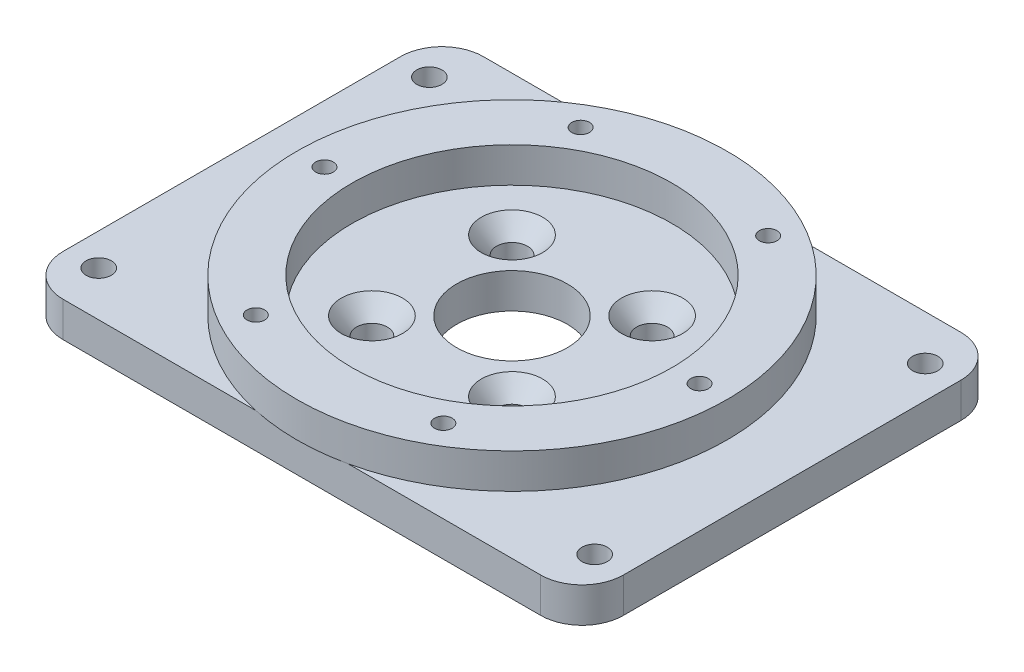
SolidWorks part; units mm, degrees
other "mainValvePlate"
other "motorRingMount"
ref_plane "Front Plane" through (0, 0, 0) normal (0, 0, 1) x (1, 0, 0)
ref_plane "Top Plane" through (0, 0, 0) normal (0, 1, 0) x (1, 0, 0)
ref_plane "Right Plane" through (0, 0, 0) normal (1, 0, 0) x (0, 0, -1)
sketch "Sketch1" plane through (0, 0, 0) normal (0, 1, 0) x (1, 0, 0)
  line L0 (0, 0) -> (0, -19.6757) construction
  line L6 (-50.8, -38.1) -> (50.8, -38.1)
  line L7 (0, 0) -> (-17, -29.4449) construction
  line L8 (0, 0) -> (-34, 0) construction
  line L9 (0, 0) -> (-17, 29.4449) construction
  line L10 (0, 0) -> (17, 29.4449) construction
  line L11 (0, 0) -> (34, 0) construction
  line L12 (0, 0) -> (17, -29.4449) construction
  line L13 (-50.8, -38.1) -> (-50.8, 38.1)
  line L14 (-50.8, 38.1) -> (50.8, 38.1)
  line L15 (50.8, -38.1) -> (50.8, 38.1)
  line L16 (-50.8, -38.1) -> (50.8, 38.1) construction
  line L17 (-50.8, 38.1) -> (50.8, -38.1) construction
  circle A0 centre (0, 0) radius 34 construction
  point P0 (0, 0)
  point P8 (0, -34)
  point P9 (44.958, -29.972)
  point P12 (-17, -29.4449)
  point P13 (-44.958, -29.972)
  point P20 (-44.958, 29.972)
  point P22 (44.958, 29.972)
  dimension "D1" = 68
  dimension "D2" = 76.2
  dimension "D3" = 101.6
  dimension "D4" = 30
  dimension "D5" = 6
  dimension "D6" = 44.958
  dimension "D7" = 29.972
extrude "Boss-Extrude1" add sketch "Sketch1" along normal blind 6.35
sketch "Sketch4" plane through (0, 0, 0) normal (0, -1, 0) x (1, 0, 0)
  circle A0 centre (-44.958, 29.972) radius 2.286
  circle A1 centre (-44.958, -29.972) radius 2.286
  circle A2 centre (44.958, -29.972) radius 2.286
  circle A3 centre (44.958, 29.972) radius 2.286
  circle A5 centre (0, 0) radius 10.033
  dimension "D1" = 4.572
  dimension "D2" = 20.066
extrude "Cut-Extrude1" cut sketch "Sketch4" against normal through all contours A0 | A1 | A2 | A3 | A5 region at (-44.958, 0, 29.972) region at (-44.958, 0, -29.972) region at (44.958, 0, -29.972) region at (44.958, 0, 29.972) region at (0, 0, 0)
sketch "Sketch6" plane through (0, 6.35, 0) normal (0, 1, 0) x (1, 0, 0)
  line L1 (-12.7, -12.7) -> (12.7, -12.7) construction
  line L2 (-12.7, -12.7) -> (-12.7, 12.7) construction
  line L3 (-12.7, 12.7) -> (12.7, 12.7) construction
  line L4 (12.7, -12.7) -> (12.7, 12.7) construction
  line L5 (-12.7, -12.7) -> (12.7, 12.7)
  line L6 (-12.7, 12.7) -> (12.7, -12.7)
  line L7 (0, 0) -> (0, 18.6441) construction
  line L8 (0, -41.91) -> (0, 41.91) construction
  point P0 (0, 0)
  point P1 (12.7, 12.7)
  point P2 (-12.7, -12.7)
  point P3 (-12.7, 12.7)
  point P4 (12.7, -12.7)
  dimension "D1" = 25.4
hole_wizard "CSK for #12 Flat Head Machine Screw3" positions "Sketch6" profile "Sketch10" countersink size "#12" standard "ANSI Inch" end condition up to next
sketch "Sketch10" plane through (12.7, 6.35, 12.7) normal (1, 0, 0) x (0, 0, 1)
  line L0 (0, 0) -> (0, 6.35)
  line L1 (0, 6.35) -> (2.8067, 6.35)
  line L2 (2.8067, 6.35) -> (2.8067, 3.1703)
  line L3 (2.8067, 3.1703) -> (5.5626, 0)
  line L5 (5.5626, 0) -> (0, 0)
  line L6 (-2.8067, 3.1703) -> (-5.5626, 0) construction
  line L11 (0, -6.35) -> (0, 107.95) construction
  dimension "Thru Hole Dia." = 5.6134
  dimension "Thru Hole Depth" = 6.35
  dimension "Near C'Sink Dia." = 11.1252
  dimension "Near C'Sink Angle" = 82
fillet "Fillet1" radius 7.5 4 edges at (50.8, 3.175, 38.1) (50.8, 3.175, -38.1) (-50.8, 3.175, -38.1) (-50.8, 3.175, 38.1)
sketch "Sketch12" plane through (0, 6.35, 0) normal (0, 1, 0) x (1, 0, 0)
  line L0 (34, 0) -> (39, 0) construction
  line L1 (34, 0) -> (29, 0) construction
  circle A0 centre (0, 0) radius 39
  circle A1 centre (0, 0) radius 29
  dimension "D1" = 5
extrude "Boss-Extrude3" add sketch "Sketch12" along normal blind 6.35 separate body
hole_wizard "CSK for M3 SFHCS1" positions "Sketch15" profile "Sketch16" countersink size "M3" standard "ANSI Metric" end condition through all
sketch "Sketch15" plane through (0, 0, 0) normal (0, -1, 0) x (-1, 0, 0)
  point P0 (-17, 29.4449)
  point P3 (-34, 0)
  point P6 (-17, -29.4449)
  point P9 (17, -29.4449)
  point P12 (34, 0)
  point P15 (17, 29.4449)
sketch "Sketch16" plane through (17, 0, -29.4449) normal (1, 0, 0) x (0, 0, -1)
  line L0 (0, 0) -> (0, 12.7)
  line L1 (0, 12.7) -> (1.6, 12.7)
  line L2 (1.6, 12.7) -> (1.6, 1.76)
  line L3 (1.6, 1.76) -> (3.36, 0)
  line L5 (3.36, 0) -> (0, 0)
  line L6 (-1.6, 1.76) -> (-3.36, 0) construction
  line L11 (0, -6.35) -> (0, 107.95) construction
  dimension "Thru Hole Dia." = 3.2
  dimension "Thru Hole Depth" = 12.7
  dimension "Near C'Sink Dia." = 6.72
  dimension "Near C'Sink Angle" = 90
